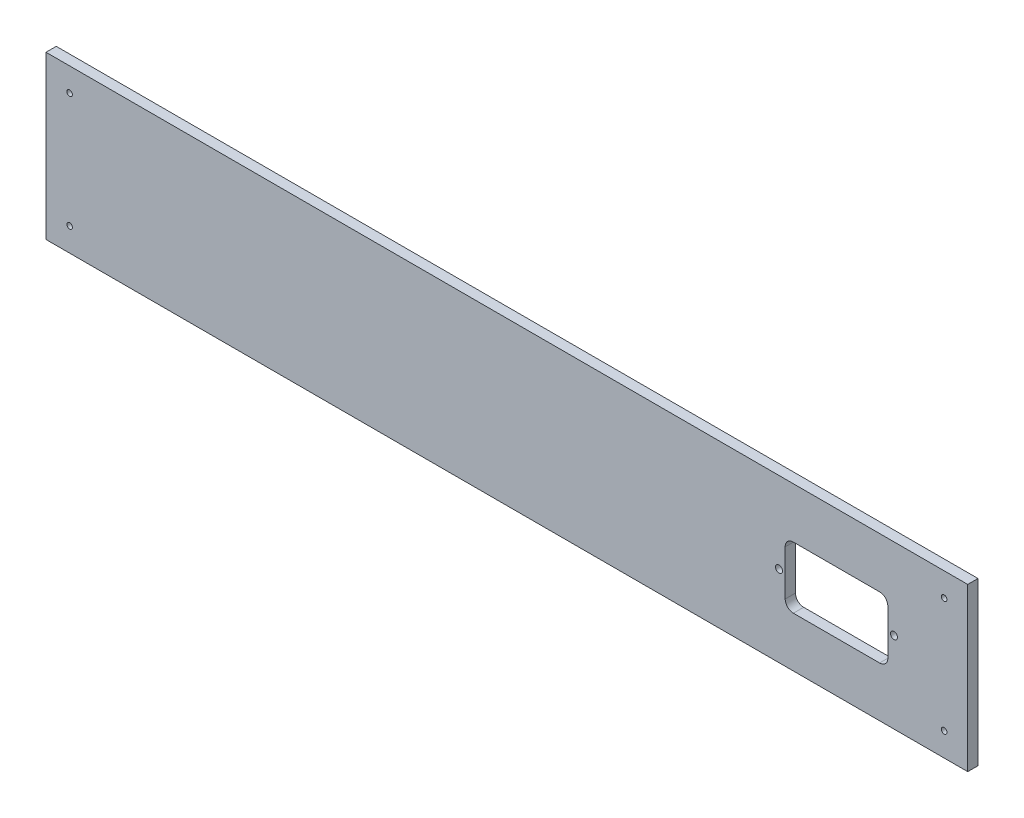
SolidWorks part; units mm, degrees
ref_plane "Piano frontale" through (0, 0, 0) normal (0, 0, 1) x (1, 0, 0)
ref_plane "Piano superiore" through (0, 0, 0) normal (0, 1, 0) x (1, 0, 0)
ref_plane "Piano destro" through (0, 0, 0) normal (1, 0, 0) x (0, 0, -1)
sketch "f" plane through (0, 0, 0) normal (0, 0, 1) x (1, 0, 0)
  line L0 (0, 0) -> (0, 79)
  line L1 (0, 79) -> (449, 79)
  line L2 (449, 79) -> (449, 0)
  line L3 (449, 0) -> (0, 0)
  line L4 (0, 39.5) -> (449, 39.5) construction
  line L5 (224.5, 42) -> (224.5, 123.488) construction
  line L10 (449, 79) -> (224.5, 0) construction
  line L11 (334, 39.5) -> (334, 81.5) construction
  line L12 (224.5, 0) -> (0, 79) construction
  line L13 (112.25, 42) -> (112.25, 84) construction
  circle A0 centre (11.5, 67.5) radius 1.3617
  circle A1 centre (437.5, 67.5) radius 1.3617
  circle A2 centre (11.5, 11.5) radius 1.3617
  circle A3 centre (437.5, 11.5) radius 1.3617
  dimension "D3" = 11.5
  dimension "D4" = 11.5
  dimension "D1" = 79
  dimension "D2" = 449
extrude "Estrusione-Estrusione1" add sketch "f" along normal blind 5
sketch "Sketch1" plane through (0, 0, 0) normal (0, 0, -1) x (-1, 0, 0)
  line L0 (0, 39.5) -> (-449, 39.5) construction
  line L1 (0, 79) -> (0, 0) construction
  line L2 (-449, 0) -> (-449, 79) construction
  line L7 (-364.0746, 54.3949) -> (-406.0746, 54.3949)
  line L8 (-360.0746, 50.3949) -> (-360.0746, 28.3949)
  line L9 (-364.0746, 24.3949) -> (-406.0746, 24.3949)
  line L10 (-410.0746, 50.3949) -> (-410.0746, 28.3949)
  arc A4 (-360.0746, 50.3949) -> (-364.0746, 54.3949) centre (-364.0746, 50.3949) ccw
  arc A5 (-360.0746, 28.3949) -> (-364.0746, 24.3949) centre (-364.0746, 28.3949) cw
  arc A6 (-406.0746, 24.3949) -> (-410.0746, 28.3949) centre (-406.0746, 28.3949) cw
  arc A7 (-410.0746, 50.3949) -> (-406.0746, 54.3949) centre (-406.0746, 50.3949) cw
  circle A8 centre (-413.0612, 39.5055) radius 1.7
  circle A9 centre (-357.0612, 39.5055) radius 1.7
extrude "Extrude1" cut sketch "Sketch1" against normal through all
